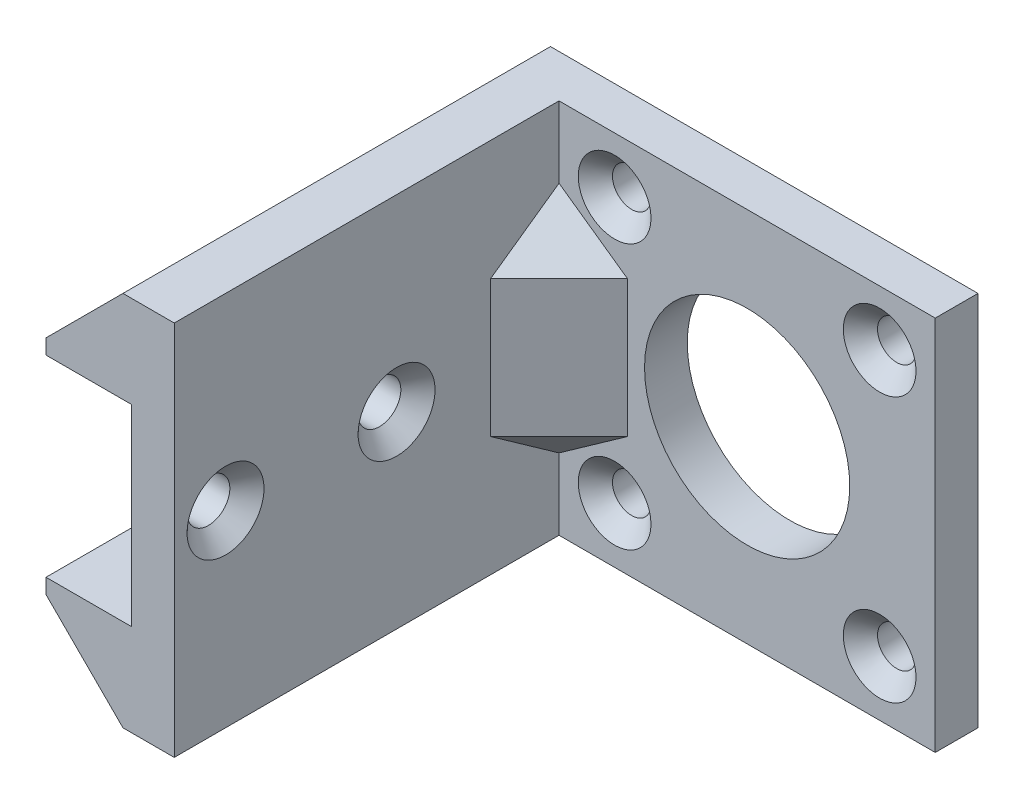
SolidWorks part; units mm, degrees
ref_plane "Top Plane" through (0, 0, 0) normal (0, 0, 1) x (1, 0, 0)
ref_plane "Right Plane" through (0, 0, 0) normal (0, 1, 0) x (1, 0, 0)
ref_plane "Front Plane" through (0, 0, 0) normal (1, 0, 0) x (0, 0, -1)
sketch "Sketch1" plane through (0, 0, 0) normal (0, 0, 1) x (1, 0, 0)
  line L0 (22, -22) -> (-22, 22) construction
  line L1 (22, 22) -> (-22, 22)
  line L2 (22, 22) -> (22, -22)
  line L3 (22, -22) -> (-22, -22)
  line L4 (-22, 22) -> (-22, -22)
  circle A0 centre (15.5, 15.5) radius 2.25
  circle A1 centre (15.5, -15.5) radius 2.25
  circle A2 centre (-15.5, -15.5) radius 2.25
  circle A3 centre (-15.5, 15.5) radius 2.25
  circle A4 centre (0, 0) radius 12
  point P21 (0, 0)
  dimension "D1" = 4.5
  dimension "D2" = 24
  dimension "D3" = 44
extrude "Boss-Extrude1" add sketch "Sketch1" along normal blind 5
sketch "Sketch2" plane through (-22, 0, 0) normal (-1, 0, 0) x (0, 0, 1)
  line L1 (0, 22) -> (50, 22)
  line L2 (0, 22) -> (0, -22)
  line L3 (0, -22) -> (50, -22)
  line L4 (50, 22) -> (50, -22)
  line L7 (44, 0) -> (24, 0) construction
  line L9 (44, 0) -> (50, 0) construction
  line L10 (24, 0) -> (5, 0) construction
  line L11 (5, 22) -> (5, -22) construction
  circle A0 centre (44, 0) radius 2.5
  circle A1 centre (24, 0) radius 2.5
  dimension "D4" = 5
  dimension "D1" = 50
  dimension "D2" = 6
  dimension "D3" = 20
extrude "Boss-Extrude2" add sketch "Sketch2" along normal blind 5
sketch "Sketch3" plane through (0, 0, 0) normal (0, 1, 0) x (1, 0, 0)
  line L0 (-14, -5) -> (-22, -13)
  line L1 (-22, -13) -> (-22, -5)
  line L2 (-22, -5) -> (-14, -5)
  dimension "D1" = 8
extrude "Boss-Extrude3" add sketch "Sketch3" along normal mid plane 30
chamfer "Chamfer1" distance 7 angle 45 2 edges at (-18, -15, 9) (-18, 15, 9)
chamfer "Chamfer2" distance 2 angle 45 2 edges at (-22, -2.5, 44) (-22, -2.5, 24)
sketch "Sketch4" plane through (-27, 0, 0) normal (-1, 0, 0) x (0, 0, 1)
  line L0 (0, 22) -> (0, -22) construction
  line L1 (50, 22) -> (0, 22)
  line L2 (50, 22) -> (50, 11.25)
  line L3 (50, 11.25) -> (0, 11.25)
  line L4 (0, 22) -> (0, 11.25)
  line L6 (50, -22) -> (0, -22)
  line L7 (50, -22) -> (50, -11.25)
  line L8 (50, -11.25) -> (0, -11.25)
  line L9 (0, -22) -> (0, -11.25)
  dimension "D1" = 22.5
extrude "Boss-Extrude4" add sketch "Sketch4" along normal blind 10
chamfer "Chamfer3" distance 9 angle 45 2 edges at (-37, -22, 25) (-37, 22, 25)
chamfer "Chamfer4" distance 2 angle 45 4 edges at (-13.25, -15.5, 5) (17.75, -15.5, 5) (-13.25, 15.5, 5) (17.75, 15.5, 5)
sketch "Sketch5" [suppressed] plane through (0, 0, 0) normal (0, 0, -1) x (-1, 0, 0)
  line L10 (-22, -22) -> (28, -22)
  line L11 (28, -22) -> (37, -13)
  line L12 (37, -13) -> (37, -11.25)
  line L13 (37, -11.25) -> (27, -11.25)
  line L14 (27, -11.25) -> (27, 11.25)
  line L15 (27, 11.25) -> (37, 11.25)
  line L16 (37, 11.25) -> (37, 13)
  line L17 (37, 13) -> (28, 22)
  line L18 (28, 22) -> (-22, 22)
  line L19 (-22, 22) -> (-22, -22)
  line L20 (-22, -22) -> (28, -22)
  line L21 (28, -22) -> (37, -13)
  line L22 (37, -13) -> (37, -11.25)
  line L23 (37, -11.25) -> (27, -11.25)
  line L24 (27, -11.25) -> (27, 11.25)
  line L25 (27, 11.25) -> (37, 11.25)
  line L26 (37, 11.25) -> (37, 13)
  line L27 (37, 13) -> (28, 22)
  line L28 (28, 22) -> (-22, 22)
  line L29 (-22, 22) -> (-22, -22)
  circle A0 centre (15.5, 15.5) radius 2.25 construction
  circle A1 centre (15.5, -15.5) radius 2.25 construction
  circle A2 centre (-15.5, 15.5) radius 2.25 construction
  circle A3 centre (-15.5, -15.5) radius 2.25 construction
  circle A4 centre (15.5, 15.5) radius 2.25
  circle A5 centre (15.5, -15.5) radius 2.25
  circle A6 centre (-15.5, 15.5) radius 2.25
  circle A7 centre (-15.5, -15.5) radius 2.25
  circle A8 centre (0, 0) radius 9.7
  dimension "D2" = 19.4
  dimension "D1" = 0
extrude "Boss-Extrude5" [suppressed] add sketch "Sketch5" along normal blind 6
